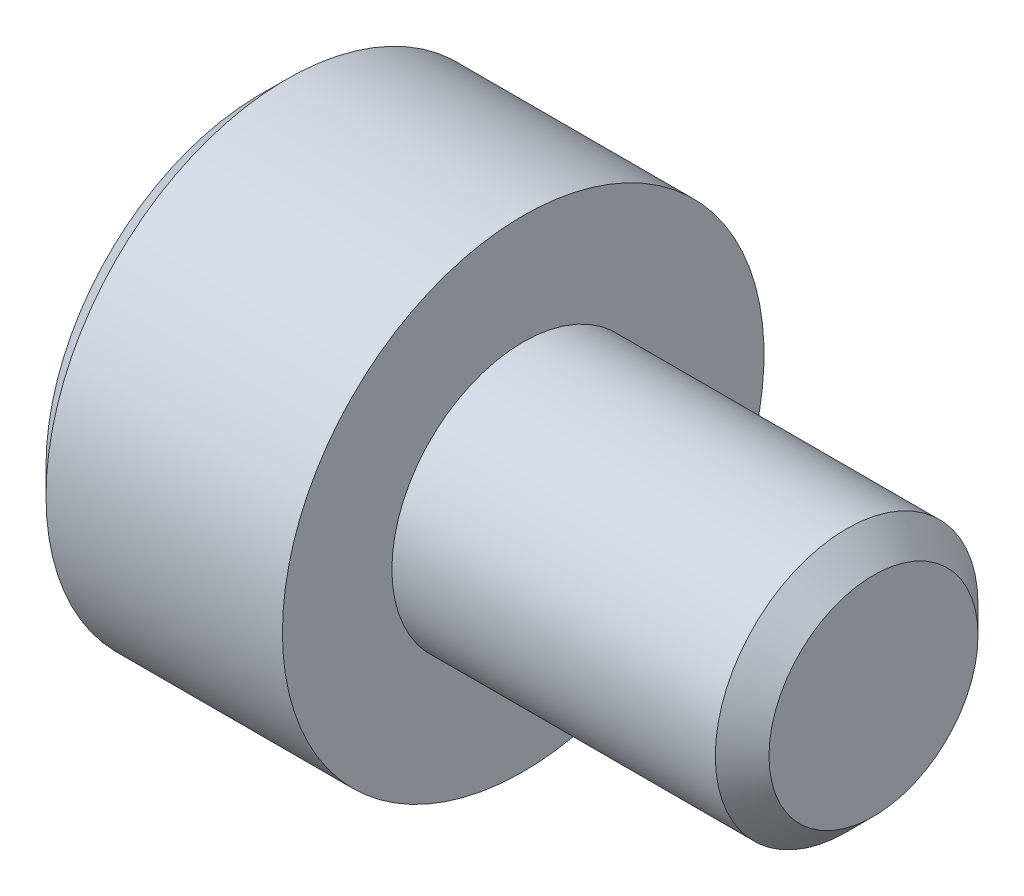
SolidWorks part; units mm, degrees
ref_plane "Front Plane" through (0, 0, 0) normal (0, 0, 1) x (1, 0, 0)
ref_plane "Top Plane" through (0, 0, 0) normal (0, 1, 0) x (1, 0, 0)
ref_plane "Right Plane" through (0, 0, 0) normal (1, 0, 0) x (0, 0, -1)
ref_plane "Plane1" through (1, 0, 0) normal (1, 0, 0) x (0, 0, -1)
ref_axis "Axis_X" through (-3.35, 0, 0) along (1, 0, 0)
ref_axis "Axis_Y" through (0, 3.025, 0) along (0, -1, 0)
ref_axis "Axis_Z" through (0, 0, -3.025) along (0, 0, 1)
sketch "Sketch1" plane through (0, 0, 0) normal (0, 0, 1) x (1, 0, 0)
  line L0 (-3, 0) -> (4, 0)
  line L1 (4, 0) -> (4, -1.1935)
  line L2 (4, -1.1935) -> (3.6935, -1.5)
  line L3 (3.6935, -1.5) -> (0, -1.5)
  line L4 (0, -1.5) -> (0, -2.75)
  line L5 (0, -2.75) -> (-2.7, -2.75)
  line L6 (-2.7, -2.75) -> (-3, -2.45)
  line L7 (-3, -2.45) -> (-3, 0)
  line L8 (0, 0) -> (-3, 0) construction
  line L9 (4, 1.1935) -> (3.6935, 1.5) construction
  line L10 (-3, 2.45) -> (-2.7, 2.75) construction
  point P16 (3.5, -1.5)
  dimension "A" = 5.5
  dimension "E" = 3
  dimension "MSM_1" = 2.387
  dimension "MSM_2" = 45
  dimension "MSM_3" = 0.3
  dimension "L" = 4
  dimension "Pitch_1" = 0.5
revolve "Revolve1" add sketch "Sketch1" angle 360 about axis through (-3.35, 0, 0) along (1, 0, 0)
sketch "Sketch2" plane through (-3, 0, 0) normal (-1, 0, 0) x (0, 0, 1)
  line L1 (0, 1.4434) -> (-1.25, 0.7217)
  line L2 (-1.25, 0.7217) -> (-1.25, -0.7217)
  line L3 (-1.25, -0.7217) -> (0, -1.4434)
  line L4 (0, -1.4434) -> (1.25, -0.7217)
  line L5 (1.25, -0.7217) -> (1.25, 0.7217)
  line L6 (1.25, 0.7217) -> (0, 1.4434)
  circle A0 centre (0, 0) radius 1.25 construction
  dimension "B" = 2.5
extrude "Cut-Extrude1" cut sketch "Sketch2" against normal blind 1.5
ref_plane "Dim. B_s" through (4, 0, 0) normal (1, 0, 0) x (0, 0, -1)
sketch "Sketch3" plane through (0, 0, 0) normal (0, 0, 1) x (1, 0, 0)
  line L0 (0, 0) -> (4, 0) construction
  line L1 (4, -1.3128) -> (4, 1.3128) construction
  line L3 (3.99, 1.5) -> (4, 1.5)
  line L5 (3.99, 1.5) -> (3.99, 1.49)
  line L6 (3.99, 1.49) -> (4, 1.49)
  line L7 (4, 1.5) -> (4, 1.49)
  line L8 (1, 1.5) -> (1.01, 1.5)
  line L9 (1, 1.5) -> (1, 1.49)
  line L10 (1, 1.49) -> (1.01, 1.49)
  line L11 (1.01, 1.5) -> (1.01, 1.49)
  dimension "MSM_5" = 0.01
  dimension "A_s" = 3
revolve "Cut-Revolve1" [suppressed] cut sketch "Sketch3" angle 360 about L0
equation "\"Factor\"= 1.082532"
equation "\"ATD_1\"= 4.134"
equation "\"L_s\"= 10"
equation "\"L_s\"= IIF ( ( \"M\" = 12 and \"L\" > 50 ) , 36 , IIF ( ( \"M\" = 10 and \"L\" > 40 ) , 32 , IIF ( ( \"M\" = 8 and \"L\" > 35 ) , 28 , IIF ( ( \"M\" = 6 and \"L\" > 30 ) , 24 , IIF ( ( \"M\" = 5 and \"L\" > 25 ) , 22 , IIF ( ( \"M\" = 4 and \"L\" > 25 ) , 20 , IIF ( ( \"M\" = 3 and \"L\" > 20 ) , 18 , \"L\" ) ) ) ) ) ) )"
equation "\"A\"= IIF ( \"M\" = 12 , 18 , IIF ( \"M\" = 10 , 16 , IIF ( \"M\" = 8 , 13 , IIF ( \"M\" = 6 , 10 , IIF ( \"M\" = 5 , 8.5 , IIF ( \"M\" = 4 , 7 , IIF ( \"M\" = 3 , 5.5 , IIF ( \"M\" = 2.6 or \"M\" = 2.5 , 4.5 , 3.8 ) ) ) ) ) ) ) )"
equation "\"E\"= \"M\""
equation "\"B\"= IIF ( \"M\" = 12 , 10 , IIF ( \"M\" = 10 , 8 , IIF ( \"M\" = 8 , 6 , IIF ( \"M\" = 6 , 5 , IIF ( \"M\" = 5 , 4 , IIF ( \"M\" = 4 , 3 , IIF ( \"M\" = 3 , 2.5 , IIF ( \"M\" = 2.6 or \"M\" = 2.5 , 2 , 1.5 ) ) ) ) ) ) ) )"
equation "\"MSM_4\"= \"M\" * 0.5"
equation "\"MSM_1\"= IIF ( \"M\" = 12 , 9.853 , IIF ( \"M\" = 10 , 8.16 , IIF ( \"M\" = 8 , 6.466 , IIF ( \"M\" = 6 , 4.773 , IIF ( \"M\" = 5 , 4.019 , IIF ( \"M\" = 4 , 3.141 , IIF ( \"M\" = 3 , 2.387 , IIF ( \"M\" = 2.6 , 2.048 , IIF ( \"M\" = 2.5 , 1.948 , 1.509 ) ) ) ) ) ) ) ) )"
equation "\"MSM_2\"= 45"
equation "\"MSM_3\"= IIF ( \"M\" = 2.6 , 0.26 , \"E\" * 0.1 )"
equation "\"Thread1\" = IIF ( ( ( \"M\" = 12 ) and ( \"L\" > 50 ) ) or ( ( \"M\" = 10 ) and ( \"L\" > 40 ) ) or ( ( \"M\" = 8 ) and ( \"L\" > 35 ) ) or ( ( \"M\" = 6 ) and ( \"L\" > 30 ) ) or ( ( \"M\" = 5 ) and ( \"L\" > 25 ) ) or ( ( \"M\" = 4 ) and ( \"L\" > 25 ) ) or ( \"M\" = 3 ) and ( \"L\" > 2 ) , \"suppressed\" , \"unsuppressed\" )"
equation "\"Thread2\" = IIF ( ( ( \"M\" = 12 ) and ( \"L\" > 50 ) ) or ( ( \"M\" = 10 ) and ( \"L\" > 40 ) ) or ( ( \"M\" = 8 ) and ( \"L\" > 35 ) ) or ( ( \"M\" = 6 ) and ( \"L\" > 30 ) ) or ( ( \"M\" = 5 ) and ( \"L\" > 25 ) ) or ( ( \"M\" = 4 ) and ( \"L\" > 25 ) ) or ( \"M\" = 3 ) and ( \"L\" > 2 ) , \"unsuppressed\" , \"suppressed\" )"
equation "\"MSM_5\"= 0.01"
equation "\"Cut-Revolve1\"= IIF ( \"TYP\" = 2 , \"unsuppressed\" , \"suppressed\" )"
equation "\"Pitch_1\"= IIF ( \"M\" = 12 , 1.75 , IIF ( \"M\" = 10 , 1.5 , IIF ( \"M\" = 8 , 1.25 , IIF ( \"M\" = 6 , 1 , IIF ( \"M\" = 5 , 0.8 , IIF ( \"M\" = 4 , 0.7 , IIF ( \"M\" = 3 , 0.5 , IIF ( \"M\" = 2.6 or \"M\" = 2.5 , 0.45 , 0.4 ) ) ) ) ) ) ) )"
equation "\"ATD_2\"= round ( \"M\" - \"Factor\" * \"Pitch_1\" , 3 )"
